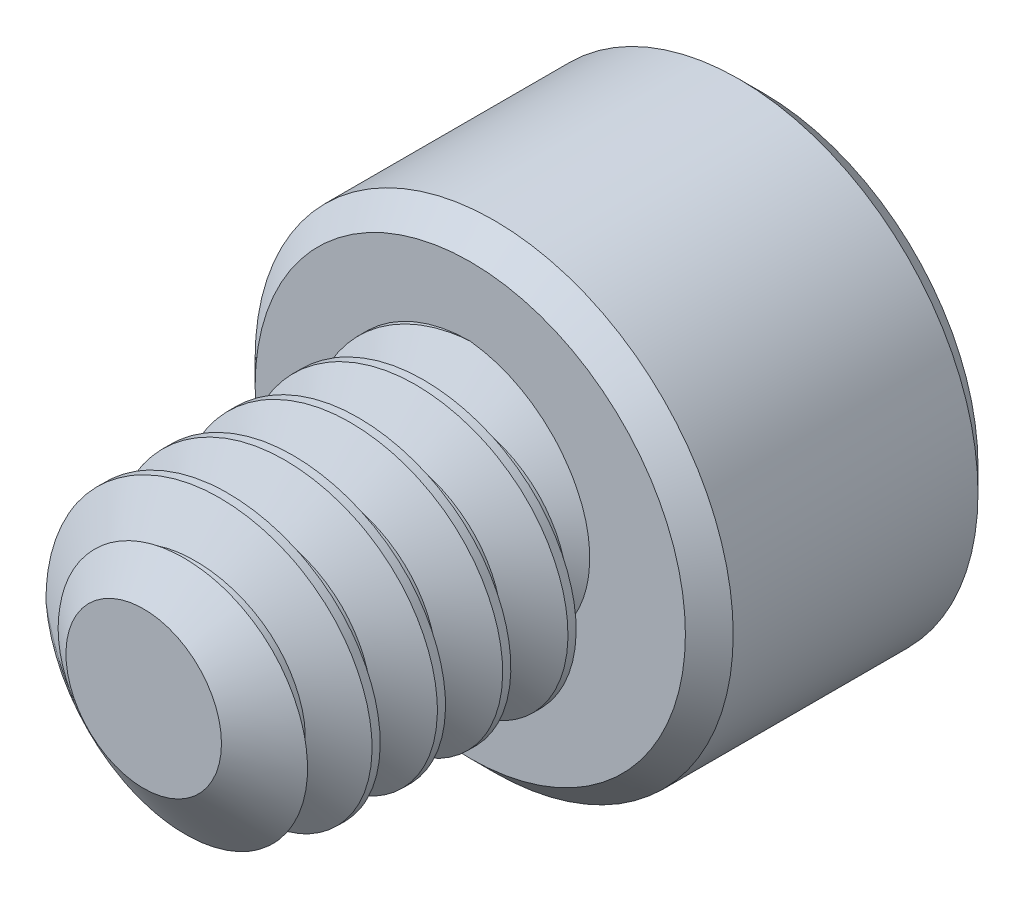
SolidWorks part; units mm, degrees
other "DetailItem1"
ref_plane "Front Plane" through (0, 0, 0) normal (0, 0, 1) x (1, 0, 0)
ref_plane "Top Plane" through (0, 0, 0) normal (0, 1, 0) x (1, 0, 0)
ref_plane "Right Plane" through (0, 0, 0) normal (1, 0, 0) x (0, 0, -1)
sketch "Sketch1" plane through (0, 0, 0) normal (0, 0, 1) x (1, 0, 0)
  circle A0 centre (0, 0) radius 1.4224
  dimension "OD" = 2.8448
extrude "Extrude1" add sketch "Sketch1" against normal blind 3.175
sketch "Sketch2" plane through (0, 0, 0) normal (0, 0, 1) x (1, 0, 0)
  circle A0 centre (0, 0) radius 1.4224 construction
  circle A1 centre (0, 0) radius 1.4224
curve "Helix/Spiral1" pitch 0.635 height 3.81 radius 1.4224 centre (0, 0, 0) axis (0, 0, -1) start towards (0, 1, 0) parameters "pitch"=0.635
sketch "Sketch3" plane through (0, 0, 0) normal (1, 0, 0) x (0, 0, -1)
  line L0 (-0.5556, 1.4224) -> (-0.3175, 1.01)
  line L1 (-0.3175, 1.01) -> (-0.2381, 1.01)
  line L2 (-0.2381, 1.01) -> (0, 1.4224)
  line L3 (-0.5556, 1.4224) -> (0, 1.4224)
  line L4 (-0.2778, 1.4224) -> (-0.2778, 1.01) construction
  line L5 (-0.4366, 1.2162) -> (-0.1191, 1.2162) construction
  line L6 (0, 1.4224) -> (0, -1.4224) construction
  dimension "D1" = 0.0794
  dimension "D2" = 0.3175
  dimension "D3" = 60
sweep "Cut-Sweep1" cut profiles "Sketch3" path "Helix/Spiral1" align with end faces yes
sketch "Sketch4" plane through (0, 0, 0) normal (1, 0, 0) x (0, 0, -1)
  line L0 (0.4666, 1.4224) -> (0, 0.756)
  line L1 (0, 0.756) -> (0, 1.4224)
  line L2 (0.4666, 1.4224) -> (0, 1.4224)
  line L3 (-0.5556, 1.4224) -> (0, 1.4224) construction
  line L4 (0, 0) -> (7.0209, 0) construction
  dimension "D1" = 55
  dimension "D2" = 0.254
revolve "Cut-Revolve1" cut sketch "Sketch4" angle 360 about L4
sketch "Sketch6" plane through (0, 0, -3.175) normal (0, 0, -1) x (-1, 0, 0)
  circle A0 centre (0, 0) radius 2.3241
  dimension "head dia" = 4.6482
extrude "Extrude2" add sketch "Sketch6" along normal blind 2.8448
sketch "Sketch7" plane through (0, 0, -6.0198) normal (0, 0, -1) x (-1, 0, 0)
  line L1 (0, 1.3748) -> (-1.1906, 0.6874)
  line L2 (-1.1906, 0.6874) -> (-1.1906, -0.6874)
  line L3 (-1.1906, -0.6874) -> (0, -1.3748)
  line L4 (0, -1.3748) -> (1.1906, -0.6874)
  line L5 (1.1906, -0.6874) -> (1.1906, 0.6874)
  line L6 (1.1906, 0.6874) -> (0, 1.3748)
  circle A0 centre (0, 0) radius 1.1906 construction
  dimension "hex dia" = 2.3813
extrude "Cut-Extrude1" cut sketch "Sketch7" against normal blind 1.7859
sketch "Sketch8" plane through (0, 0, -6.0198) normal (0, 0, -1) x (-1, 0, 0)
  circle A0 centre (0, 0) radius 1.3748
extrude "Cut-Extrude2" cut sketch "Sketch8" against normal through all draft 45
chamfer "Chamfer1" distance 0.2324 angle 45 2 edges at (-2.3241, 0, -6.0198) (-2.3241, 0, -3.175)
sketch "Sketch10" plane through (0, 0, -3.175) normal (0, 0, 1) x (1, 0, 0)
  circle A1 centre (0, 0) radius 1.4224
  circle A2 centre (0, 0) radius 1.4224
  dimension "D1" = 0
ref_plane "Plane1" through (0, 0, -38.1) normal (0, 0, 1) x (1, 0, 0)
extrude "partial thread" [suppressed] add sketch "Sketch10" along normal up to surface (12.7 mm away) separate body up to plane "Plane1"
chamfer "Chamfer2" [suppressed] distance 0.0569 angle 45
combine bodies "Combine1" [suppressed] operation type add bodies to combine 107 108
sketch "Sketch9" plane through (0, 0, 0) normal (1, 0, 0) x (0, 0, -1)
  line L0 (0, 1.4224) -> (0, -1.4224) construction
  line L1 (1.5875, 1.4224) -> (1.5875, -1.4224) construction
  dimension "D1" = 1.5875
equation "\"D3@Helix/Spiral1\" = \"screw length@Extrude1\"+\"pitch@Helix/Spiral1\""
equation "\"D1@Sketch3\" = \"pitch@Helix/Spiral1\"*.125"
equation "\"D2@Sketch3\" = \"pitch@Helix/Spiral1\"*.5"
equation "\"D1@Cut-Extrude1\" = \"hex dia@Sketch7\"*.75"
equation "\"D1@Chamfer1\" = \"head dia@Sketch6\"*.05"
equation "\"D1@Sketch9\" = \"pitch@Helix/Spiral1\"*2.5"
equation "\"D1@Chamfer2\"=\"OD@Sketch1\"*.02"
